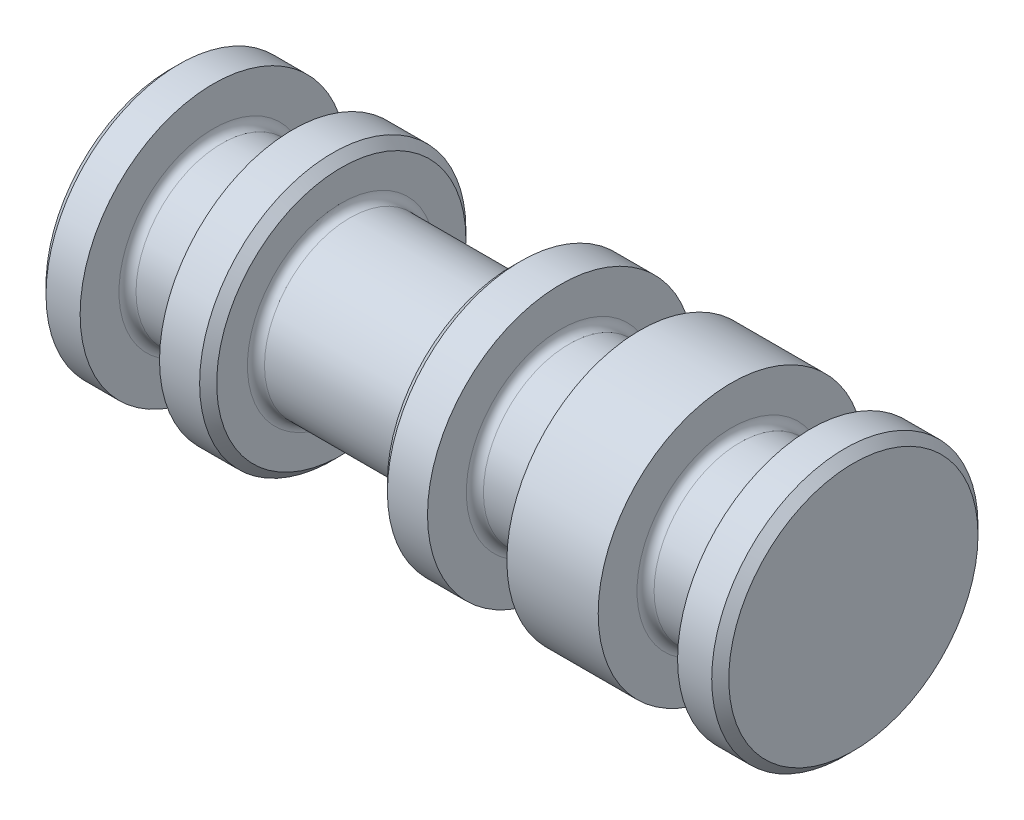
SolidWorks part; units mm, degrees
material "6063-T6"
ref_plane "Front Plane" through (0, 0, 0) normal (0, 0, 1) x (1, 0, 0)
ref_plane "Top Plane" through (0, 0, 0) normal (0, 1, 0) x (1, 0, 0)
ref_plane "Right Plane" through (0, 0, 0) normal (1, 0, 0) x (0, 0, -1)
sketch "Sketch1" plane through (0, 0, 0) normal (1, 0, 0) x (0, 0, -1)
  circle A0 centre (0, 0) radius 3.9624
  dimension "D1" = 7.9248
extrude "Boss-Extrude1" add sketch "Sketch1" along normal blind 20.32
sketch "Sketch2" plane through (0, 0, 0) normal (0, 0, 1) x (1, 0, 0)
  line L0 (-1.6174, 0) -> (23.3579, 0) construction
  line L1 (1.27, 3.9624) -> (3.6322, 3.9624)
  line L2 (3.6322, 3.9624) -> (3.6322, 2.5527)
  line L3 (3.6322, 2.5527) -> (1.27, 2.5527)
  line L4 (1.27, 2.5527) -> (1.27, 3.9624)
  line L5 (0, 3.9624) -> (0, -3.9624) construction
  line L6 (15.24, 5.6982) -> (15.24, -5.5364) construction
  line L7 (20.32, -3.9624) -> (20.32, 3.9624) construction
  line L8 (16.6878, 3.9624) -> (19.05, 3.9624)
  line L9 (19.05, 3.9624) -> (19.05, 2.5527)
  line L10 (19.05, 2.5527) -> (16.6878, 2.5527)
  line L11 (16.6878, 2.5527) -> (16.6878, 3.9624)
  line L12 (11.6078, 3.9624) -> (13.97, 3.9624)
  line L13 (13.97, 3.9624) -> (13.97, 2.5527)
  line L14 (13.97, 2.5527) -> (11.6078, 2.5527)
  line L15 (11.6078, 2.5527) -> (11.6078, 3.9624)
  line L17 (5.08, 3.9624) -> (10.16, 3.9624)
  line L18 (5.08, 3.9624) -> (5.08, 2.54)
  line L19 (5.08, 2.54) -> (10.16, 2.54)
  line L20 (10.16, 3.9624) -> (10.16, 2.54)
  dimension "D1" = 7.9248
  dimension "D2" = 5.1054
  dimension "D3" = 2.3622
  dimension "D4" = 1.27
  dimension "D5" = 5.08
  dimension "D6" = 1.27
  dimension "D7" = 6.35
  dimension "D8" = 5.08
  dimension "D9" = 10.16
  dimension "D10" = 5.08
revolve "Cut-Revolve1" cut sketch "Sketch2" angle 360 about L0
fillet "Fillet1" radius 0.254 8 edges at (19.05, 0, 2.5527) (16.6878, 0, 2.5527) (13.97, 0, 2.5527) (11.6078, 0, 2.5527) (10.16, 0, 2.54) (5.08, 0, 2.54) (3.6322, 0, 2.5527) (1.27, 0, 2.5527)
chamfer "Chamfer1" distance 0.254 angle 45 4 edges at (20.32, 0, -3.9624) (10.16, 0, 3.9624) (5.08, 0, 3.9624) (0, 0, -3.9624)
